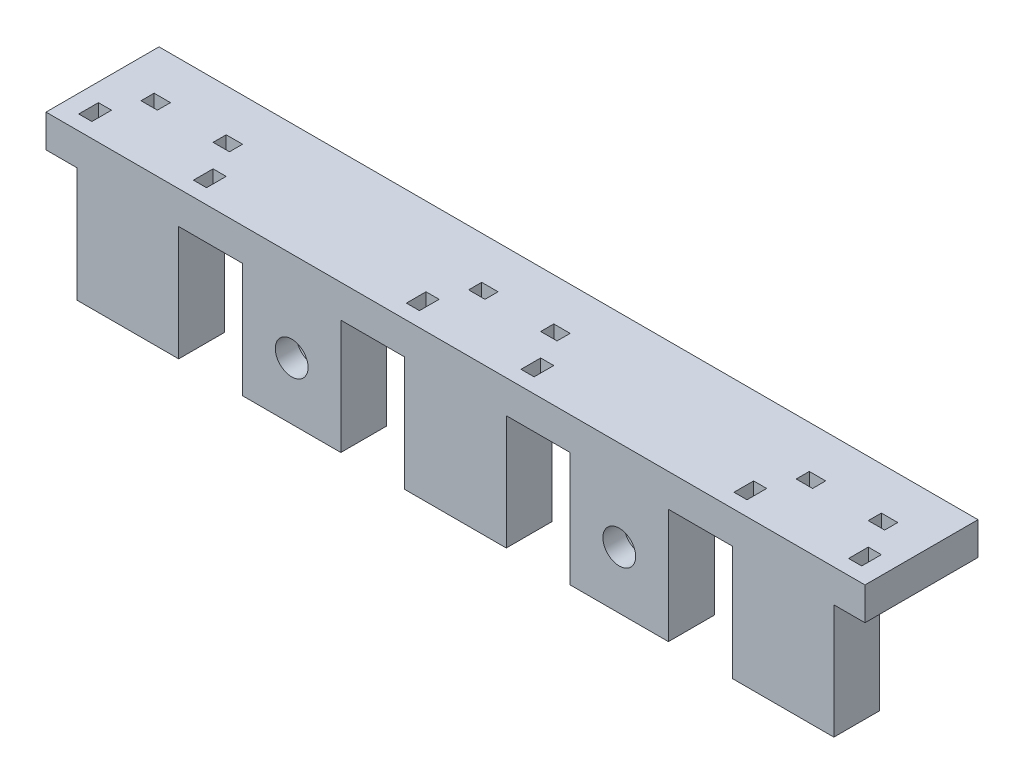
SolidWorks part; units mm, degrees
ref_plane "前视基准面" through (0, 0, 0) normal (0, 0, 1) x (1, 0, 0)
ref_plane "上视基准面" through (0, 0, 0) normal (0, 1, 0) x (1, 0, 0)
ref_plane "右视基准面" through (0, 0, 0) normal (1, 0, 0) x (0, 0, -1)
other "Configuration Table"
sketch "草图1" plane through (0, 0, 0) normal (0, 1, 0) x (1, 0, 0)
  line L1 (0, 0) -> (117.5679, 0)
  line L2 (0, 0) -> (0, -35.2117)
  line L3 (0, -35.2117) -> (117.5679, -35.2117)
  line L4 (117.5679, 0) -> (117.5679, -35.2117)
extrude "凸台-拉伸1" add sketch "草图1" along normal blind 2
sketch "草图3" plane through (0, 2, 0) normal (0, 1, 0) x (1, 0, 0)
  line L0 (117.5679, 0) -> (0, 0) construction
  line L1 (1.9, -4.8) -> (1.1, -4.8)
  line L2 (1.9, -4.8) -> (1.9, -6)
  line L3 (1.9, -6) -> (1.1, -6)
  line L4 (1.1, -4.8) -> (1.1, -6)
  line L5 (3.3, -3) -> (6.7, -3) construction
  line L6 (8.1, -4.8) -> (8.9, -4.8)
  line L7 (8.1, -4.8) -> (8.1, -6)
  line L8 (8.1, -6) -> (8.9, -6)
  line L9 (8.9, -4.8) -> (8.9, -6)
  line L10 (2.3, -2.6) -> (3.3, -2.6)
  line L11 (2.3, -2.6) -> (2.3, -3.4)
  line L12 (2.3, -3.4) -> (3.3, -3.4)
  line L13 (3.3, -2.6) -> (3.3, -3.4)
  line L14 (6.7, -2.6) -> (7.7, -2.6)
  line L15 (6.7, -2.6) -> (6.7, -3.4)
  line L16 (6.7, -3.4) -> (7.7, -3.4)
  line L17 (7.7, -2.6) -> (7.7, -3.4)
  line L18 (1.9, -5.4) -> (8.1, -5.4) construction
  line L19 (5, -3) -> (5, -5.4) construction
  line L20 (0, 0) -> (0, -35.2117) construction
  dimension "D1" = 6.2
  dimension "D2" = 0.8
  dimension "D3" = 1.2
  dimension "D4" = 1
  dimension "D5" = 0.8
  dimension "D6" = 2.4
  dimension "D7" = 3.4
  dimension "D8" = 3
  dimension "D9" = 5
extrude "切除-拉伸1" cut sketch "草图3" against normal through all
pattern_linear "阵列(线性)1" count 3 spacing 20 along (1, 0, 0) of "切除-拉伸1"
sketch "草图4" plane through (0, 0, 0) normal (0, -1, 0) x (1, 0, 0)
  line L0 (117.5679, 0) -> (0, 0) construction
  line L1 (0, 0) -> (50, 0)
  line L2 (0, 0) -> (0, 6.9)
  line L3 (0, 6.9) -> (50, 6.9)
  line L4 (50, 0) -> (50, 6.9)
  line L5 (0, 0) -> (0, 35.2117) construction
  dimension "D1" = 6.9
  dimension "D2" = 50
extrude "切除-拉伸2" cut sketch "草图4" against normal through all flip side to cut
sketch "草图5" plane through (0, 0, 0) normal (0, -1, 0) x (1, 0, 0)
  line L0 (50, 6.9) -> (0, 6.9) construction
  line L1 (41.9, 6.9) -> (48.1, 6.9)
  line L2 (41.9, 6.9) -> (41.9, 4.1)
  line L3 (41.9, 4.1) -> (48.1, 4.1)
  line L4 (48.1, 6.9) -> (48.1, 4.1)
  line L5 (41.9, 6) -> (41.9, 4.8) construction
  line L6 (48.1, 4.8) -> (48.1, 6) construction
  line L7 (1.9, 6) -> (1.9, 4.8) construction
  line L8 (21.9, 6.9) -> (28.1, 6.9)
  line L9 (21.9, 6.9) -> (21.9, 4.1)
  line L10 (21.9, 4.1) -> (28.1, 4.1)
  line L11 (28.1, 6.9) -> (28.1, 4.1)
  line L12 (1.9, 6.9) -> (8.1, 6.9)
  line L13 (1.9, 6.9) -> (1.9, 4.1)
  line L14 (1.9, 4.1) -> (8.1, 4.1)
  line L15 (8.1, 6.9) -> (8.1, 4.1)
  line L16 (8.1, 4.8) -> (8.1, 6) construction
  line L17 (21.9, 6) -> (21.9, 4.8) construction
  line L18 (28.1, 4.8) -> (28.1, 6) construction
  line L19 (8.1, 4.1) -> (12, 4.1) construction
  line L20 (12, 6.9) -> (18, 6.9)
  line L21 (12, 6.9) -> (12, 4.1)
  line L22 (12, 4.1) -> (18, 4.1)
  line L23 (18, 6.9) -> (18, 4.1)
  line L24 (32, 6.9) -> (38, 6.9)
  line L25 (32, 6.9) -> (32, 4.1)
  line L26 (32, 4.1) -> (38, 4.1)
  line L27 (38, 6.9) -> (38, 4.1)
  line L28 (18, 4.1) -> (21.9, 4.1) construction
  line L29 (28.1, 4.1) -> (32, 4.1) construction
  line L30 (38, 4.1) -> (41.9, 4.1) construction
  dimension "D1" = 2.8
  dimension "D2" = 6
extrude "凸台-拉伸2" add sketch "草图5" along normal blind 7
sketch "草图6" plane through (0, 0, 4.1) normal (0, 0, -1) x (-1, 0, 0)
  line L0 (-38, -3.5) -> (-32, -3.5) construction
  line L1 (-38, -7) -> (-38, 0) construction
  line L2 (-32, -7) -> (-32, 0) construction
  line L3 (-18, -3.5) -> (-12, -3.5) construction
  line L4 (-18, -7) -> (-18, 0) construction
  line L5 (-12, -7) -> (-12, 0) construction
  circle A0 centre (-35, -3.5) radius 2
  circle A1 centre (-35, -3.5) radius 1
  circle A2 centre (-15, -3.5) radius 2
  circle A3 centre (-15, -3.5) radius 1
  dimension "D1" = 2
  dimension "D2" = 4
extrude "切除-拉伸3" cut sketch "草图6" against normal blind 1.5 contours A0 | A2
extrude "切除-拉伸4" cut sketch "草图6<3>" against normal through all contours A1 | A3
sketch "草图6<3>" plane through (0, 0, 4.1) normal (0, 0, -1) x (-1, 0, 0) same geometry as "草图6"
